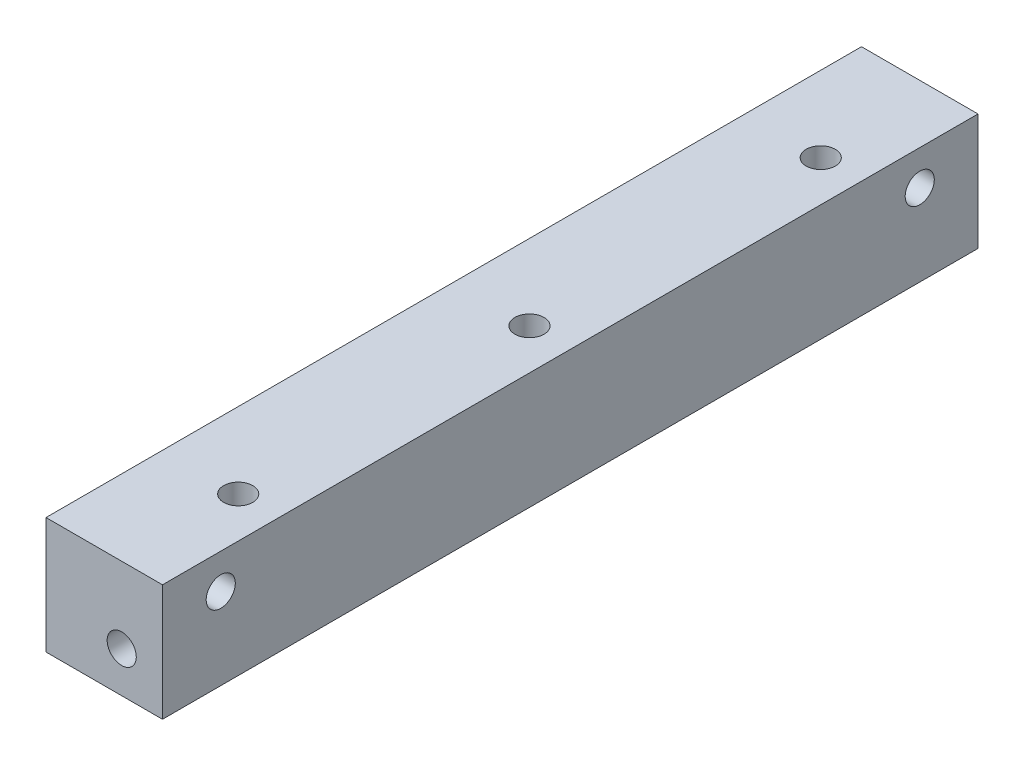
SolidWorks part; units mm, degrees
ref_plane "Ön Düzlem" through (0, 0, 0) normal (0, 0, 1) x (1, 0, 0)
ref_plane "Üst Düzlem" through (0, 0, 0) normal (0, 1, 0) x (1, 0, 0)
ref_plane "Sağ Düzlem" through (0, 0, 0) normal (1, 0, 0) x (0, 0, -1)
sketch "Çizim1" plane through (0, 0, 0) normal (0, 0, 1) x (1, 0, 0)
  line L0 (0, 20) -> (20, 0) construction
  line L1 (0, 0) -> (20, 0)
  line L2 (0, 0) -> (0, 20)
  line L3 (0, 20) -> (20, 20)
  line L4 (20, 0) -> (20, 20)
  line L5 (20, 20) -> (0, 0) construction
  point P4 (10, 10)
extrude "Yükseklik-Ekstrüzyon1" add sketch "Çizim1" along normal blind 140
sketch "Çizim2" plane through (0, 0, 0) normal (-1, 0, 0) x (0, 0, 1)
  line L0 (20, 0) -> (20, 20) construction
  line L1 (140, 0) -> (0, 0) construction
  line L2 (140, 20) -> (0, 20) construction
  line L3 (70, 0) -> (70, 20) construction
  line L4 (120, 0) -> (120, 20) construction
  line L5 (0, 20) -> (0, 0) construction
  line L6 (140, 20) -> (140, 0) construction
  line L7 (0, 7) -> (140, 7) construction
  point P16 (20, 7)
  point P17 (70, 7)
  point P18 (120, 7)
  dimension "D1" = 20
  dimension "D2" = 20
  dimension "D3" = 7
hole_wizard "Ø4.0mm Saplama Delikleri3" positions "3B Çizim1" profile "Çizim3" hole size "Ø4.0" standard "ANSI Metric"
sketch3d "3B Çizim1"
  point P0 (0, 7, 20)
  point P3 (0, 7, 70)
  point P6 (0, 7, 120)
sketch "Çizim3" plane through (0, 7, 20) normal (0, 1, 0) x (0, 0, 1)
  line L0 (0, 0) -> (0, 10)
  line L1 (0, 10) -> (2.5, 10)
  line L2 (2.5, 10) -> (2.5, 0)
  line L5 (2.5, 0) -> (0, 0)
  line L10 (0, 10) -> (-2.5, 10) construction
  line L11 (0, -6.35) -> (0, 107.95) construction
  dimension "Hole Dia." = 5
  dimension "Hole Depth" = 10
  dimension "Drill Angle" = 180
sketch "Çizim4" plane through (0, 20, 0) normal (0, 1, 0) x (1, 0, 0)
  line L0 (13, 0) -> (13, -140) construction
  line L1 (20, 0) -> (0, 0) construction
  line L2 (20, -140) -> (0, -140) construction
  line L3 (20, -140) -> (20, 0) construction
  line L4 (0, -20) -> (20, -20) construction
  line L5 (0, -70) -> (20, -70) construction
  line L6 (0, 0) -> (0, -140) construction
  line L7 (0, -120) -> (20, -120) construction
  point P19 (13, -20)
  point P20 (13, -70)
  point P21 (13, -120)
  dimension "D1" = 7
hole_wizard "Ø4.0mm Saplama Delikleri4" positions "3B Çizim2" profile "Çizim5" hole size "Ø4.0" standard "ANSI Metric"
sketch3d "3B Çizim2"
  point P0 (13, 20, 20)
  point P3 (13, 20, 70)
  point P6 (13, 20, 120)
sketch "Çizim5" plane through (13, 20, 20) normal (1, 0, 0) x (0, 0, 1)
  line L0 (0, 0) -> (0, 10)
  line L1 (0, 10) -> (2.5, 10)
  line L2 (2.5, 10) -> (2.5, 0)
  line L5 (2.5, 0) -> (0, 0)
  line L10 (0, 10) -> (-2.5, 10) construction
  line L11 (0, -6.35) -> (0, 107.95) construction
  dimension "Hole Dia." = 5
  dimension "Hole Depth" = 10
  dimension "Drill Angle" = 180
sketch "Çizim13" plane through (0, 0, 140) normal (0, 0, 1) x (1, 0, 0)
  line L0 (13, 20) -> (13, 0) construction
  line L1 (0, 0) -> (20, 0) construction
  line L2 (0, 7) -> (20, 7) construction
  line L3 (20, 0) -> (20, 20) construction
  circle A0 centre (13, 7) radius 2.5
extrude "Kes-Ekstrüzyon1" cut sketch "Çizim13" against normal blind 10
sketch "Çizim15" plane through (0, 0, 0) normal (0, 0, -1) x (-1, 0, 0)
  line L0 (-13, 20) -> (-13, 0) construction
  line L1 (0, 0) -> (-20, 0) construction
  line L2 (0, 7) -> (-20, 7) construction
  line L3 (-20, 0) -> (-20, 20) construction
  circle A0 centre (-13, 7) radius 2.5
extrude "Kes-Ekstrüzyon2" cut sketch "Çizim15" against normal blind 10
sketch "Çizim18" plane through (20, 0, 0) normal (1, 0, 0) x (0, 0, -1)
  line L0 (0, 0) -> (0, 20) construction
  line L1 (0, 20) -> (-140, 20) construction
  line L2 (-140, 0) -> (-140, 20) construction
  circle A0 centre (-10, 14) radius 2.5
  circle A1 centre (-130, 14) radius 2.5
  dimension "D1" = 10
  dimension "D2" = 6
  dimension "D3" = 10
  dimension "D4" = 6
extrude "Kes-Ekstrüzyon3" cut sketch "Çizim18" against normal blind 10
sketch "Çizim20" plane through (0, 0, 0) normal (0, -1, 0) x (1, 0, 0)
  line L0 (0, 0) -> (0, 140) construction
  line L1 (0, 0) -> (20, 0) construction
  line L2 (0, 140) -> (20, 140) construction
  circle A0 centre (6, 10) radius 2.5
  circle A1 centre (6, 130) radius 2.5
  dimension "D1" = 6
  dimension "D2" = 10
  dimension "D3" = 6
  dimension "D4" = 10
extrude "Kes-Ekstrüzyon4" cut sketch "Çizim20" against normal blind 10
